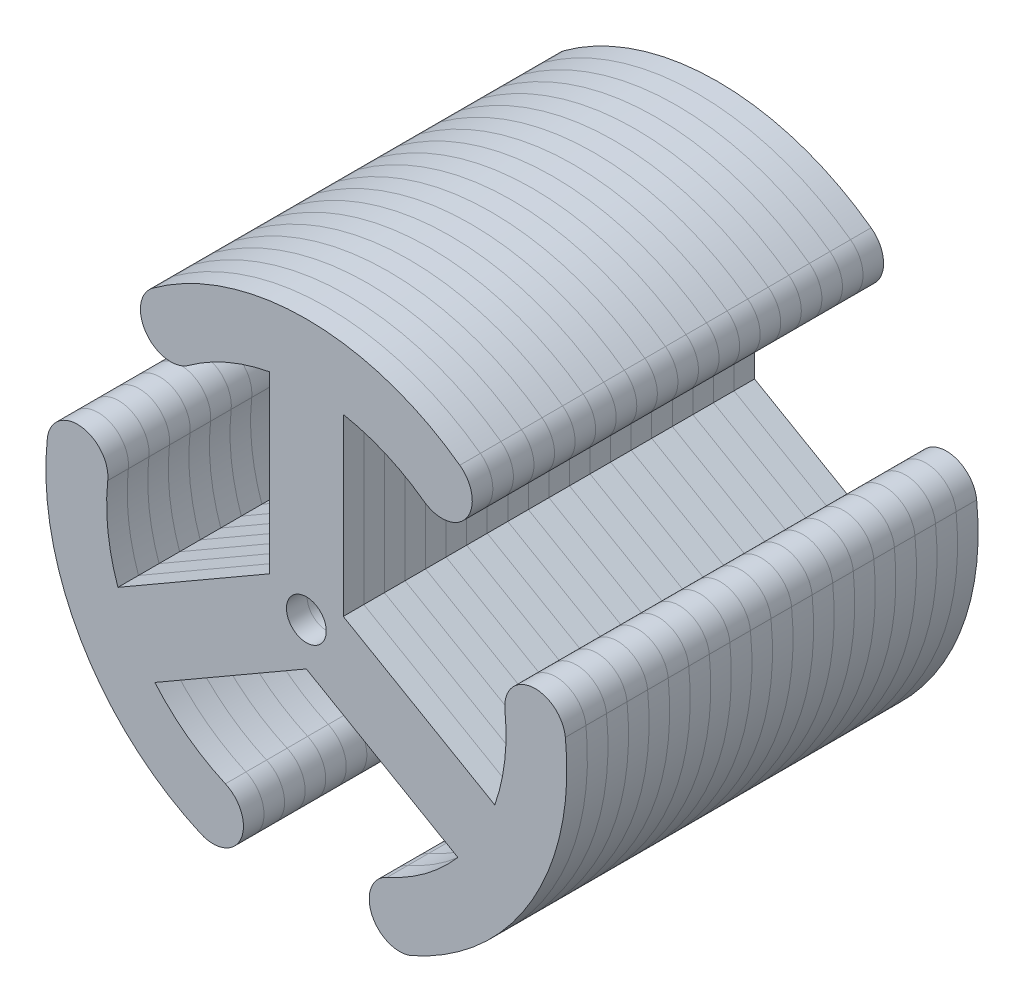
SolidWorks part; units mm, degrees
ref_plane "Front Plane" through (0, 0, 0) normal (0, 0, 1) x (1, 0, 0)
ref_plane "Top Plane" through (0, 0, 0) normal (0, 1, 0) x (1, 0, 0)
ref_plane "Right Plane" through (0, 0, 0) normal (1, 0, 0) x (0, 0, -1)
sketch "Sketch2" plane through (0, 0, 0) normal (0, 0, 1) x (1, 0, 0)
  line L0 (0, 19) -> (-16.4545, -9.5)
  line L1 (-16.4545, -9.5) -> (16.4545, -9.5)
  line L2 (16.4545, -9.5) -> (0, 19)
  line L9 (-2.6919, 0) -> (2.6919, 0)
  line L10 (-2.6919, 0) -> (-2.6919, 19)
  line L11 (-2.6919, 19) -> (2.6919, 19)
  line L12 (2.6919, 0) -> (2.6919, 19)
  circle A5 centre (0, 0) radius 19
  arc A6 (9.8862, 13.5628) -> (-9.8862, 13.5628) centre (0, 0) ccw construction
  arc A7 (11.1917, 15.354) -> (-11.1917, 15.354) centre (0, 0) ccw
  arc A8 (8.5806, 11.7717) -> (-8.5806, 11.7717) centre (0, 0) ccw
  arc A9 (8.5806, 11.7717) -> (11.1917, 15.354) centre (9.8862, 13.5628) ccw
  arc A10 (-11.1917, 15.354) -> (-8.5806, 11.7717) centre (-9.8862, 13.5628) ccw
  point P8 (0, 16.7835)
  dimension "D1" = 38
extrude "Boss-Extrude3" add sketch "Sketch2" along normal blind 1.5 contours L12 A8 L10 L9 | A9 A7 A10 A8 region at (0, 7.242, 0)
sketch "Sketch5" plane through (0, 0, 0) normal (1, 0, 0) x (0, 0, -1)
  line L0 (0, 0) -> (12.727, 0)
pattern_circular "CirPattern1" count 3 over 360 about axis through (0, 0, 0) along (0, 0, -1) of "Boss-Extrude3"
pattern_linear "LPattern1" count 20 spacing 1.5 along (0, 0, 1) of bodies 105
sketch "Sketch6" plane through (0, 0, 30) normal (0, 0, 1) x (1, 0, 0)
  circle A0 centre (0, 0) radius 1.45
extrude "Cut-Extrude1" cut sketch "Sketch6" against normal blind 31.5
